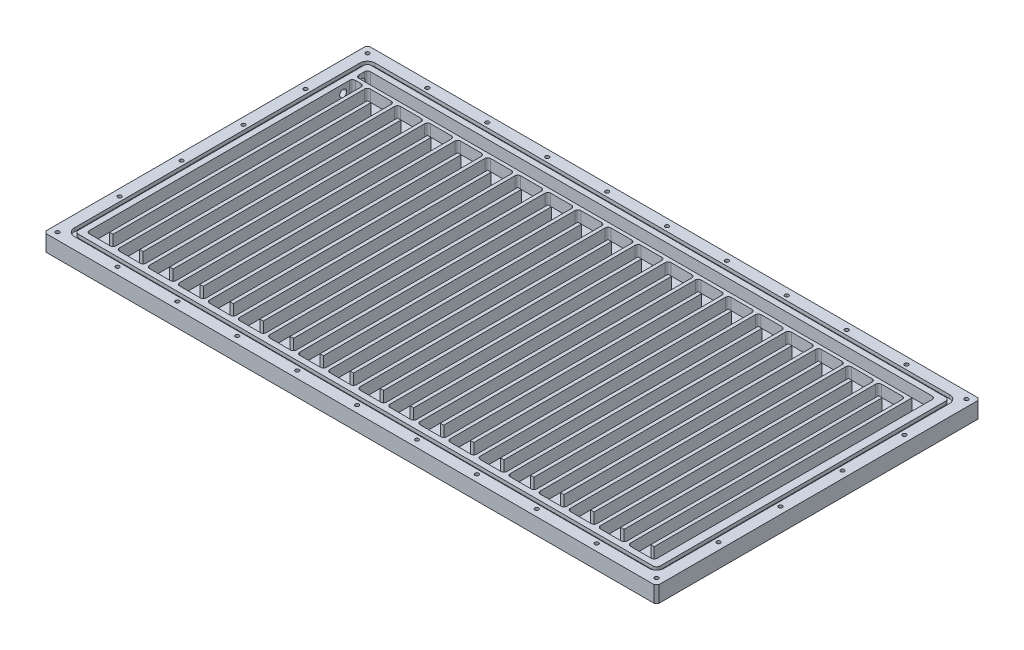
SolidWorks part; units mm, degrees
material "6063-T6"
ref_plane "Front Plane" through (0, 0, 0) normal (0, 0, 1) x (1, 0, 0)
ref_plane "Top Plane" through (0, 0, 0) normal (0, 1, 0) x (1, 0, 0)
ref_plane "Right Plane" through (0, 0, 0) normal (1, 0, 0) x (0, 0, -1)
sketch "Sketch1" plane through (0, 0, 0) normal (0, 1, 0) x (1, 0, 0)
  line L0 (265, 0) -> (265, 140)
  line L1 (0, 0) -> (265, 0)
  line L2 (0, 0) -> (0, 140)
  line L3 (0, 140) -> (265, 140)
  line L5 (213.2, 6) -> (265, 6) construction
  circle A0 centre (6, 113.2) radius 1.65 construction
  circle A1 centre (6, 59.6) radius 1.65 construction
  circle A2 centre (6, 6) radius 1.65 construction
  circle A3 centre (57.8, 6) radius 1.65 construction
  circle A4 centre (109.6, 6) radius 1.65 construction
  circle A5 centre (161.4, 6) radius 1.65 construction
  circle A6 centre (213.2, 6) radius 1.65 construction
  point P20 (265, 6)
  dimension "D3" = 3.3
  dimension "D4" = 3.3
  dimension "D5" = 3.3
  dimension "D6" = 3.3
  dimension "D7" = 3.3
  dimension "D8" = 3.3
  dimension "D9" = 3.3
  dimension "D1" = 265
  dimension "D2" = 140
  dimension "D10" = 6
  dimension "D11" = 6
  dimension "D12" = 6
  dimension "D13" = 6
  dimension "D14" = 6
  dimension "D15" = 6
  dimension "D16" = 6
  dimension "D17" = 6
  dimension "D20" = 51.8
  dimension "D21" = 51.8
  dimension "D22" = 51.8
  dimension "D23" = 51.8
  dimension "D24" = 53.6
  dimension "D25" = 53.6
  dimension "D18" = 51.8
extrude "Boss-Extrude1" add sketch "Sketch1" along normal blind 14
sketch "Sketch2" plane through (0, 14, 0) normal (0, 1, 0) x (1, 0, 0)
  line L0 (265, 140) -> (0, 140) construction
  line L1 (10, 140) -> (13.5, 140)
  line L2 (10, 140) -> (10, 10)
  line L3 (10, 10) -> (14.8949, 10)
  line L4 (13.5, 140) -> (13.5, 13.5)
  line L5 (265, 0) -> (265, 140) construction
  line L6 (14.8949, 10) -> (265, 10)
  line L8 (13.5, 13.5) -> (265, 13.5)
  line L9 (265, 10) -> (265, 13.5)
  line L10 (0, 140) -> (0, 0) construction
  line L11 (0, 0) -> (265, 0) construction
  dimension "D1" = 10
  dimension "D2" = 10
  dimension "D3" = 3.5
  dimension "D4" = 3.5
extrude "Cut-Extrude1" cut sketch "Sketch2" against normal blind 3
fillet "Fillet1" radius 3 1 edges at (13.5, 12.5, -13.5)
fillet "Fillet2" radius 6.5 1 edges at (10, 12.5, -10)
mirror "Mirror1" about plane through (265, 14, 0) normal (-1, 0, 0) of bodies 102
mirror "Mirror2" about plane through (0, 14, -140) normal (0, 0, 1) of bodies 103
hole_wizard "M4x0.7 Tapped Hole1" positions "3DSketch6" profile "Sketch13" tap size "M4x0.7" standard "BSI" end condition through all
sketch3d "3DSketch6"
  point P22 (6, 0, -113.2)
  point P24 (6, 0, -59.6)
  point P26 (6, 0, -6)
  point P28 (57.8, 0, -6)
  point P30 (109.6, 0, -6)
  point P32 (161.4, 0, -6)
  point P34 (213.2, 0, -6)
  point P36 (265, 0, -6)
cosmetic thread "Hole Thread2" parameters "D2"=4
cosmetic thread "Hole Thread3" parameters "D2"=4
cosmetic thread "Hole Thread4" parameters "D2"=4
cosmetic thread "Hole Thread5" parameters "D2"=4
cosmetic thread "Hole Thread6" parameters "D2"=4
cosmetic thread "Hole Thread7" parameters "D2"=4
cosmetic thread "Hole Thread8" parameters "D2"=4
cosmetic thread "Hole Thread9" parameters "D2"=4
sketch "Sketch13" plane through (6, 0, -113.2) normal (1, 0, 0) x (0, 0, -1)
  line L0 (0, 0) -> (0, 14)
  line L1 (0, 14) -> (1.65, 14)
  line L2 (1.65, 14) -> (1.65, 0)
  line L5 (1.65, 0) -> (0, 0)
  line L11 (0, -6.35) -> (0, 107.95) construction
  dimension "Thru Tap Drill Dia." = 3.3
  dimension "Thru Tap Drill Depth" = 14
ref_plane "Plane35" through (0, 0, -140) normal (0, 0, 1) x (1, 0, 0)
ref_plane "Plane36" through (265, 0, 0) normal (1, 0, 0) x (0, 0, -1)
mirror "Mirror3" about plane through (0, 0, -140) normal (0, 0, 1) of "M4x0.7 Tapped Hole1"
mirror "Mirror4" about plane through (265, 0, 0) normal (1, 0, 0) of "Mirror3"
sketch "Sketch3" plane through (0, 14, 0) normal (0, 1, 0) x (1, 0, 0)
  line L1 (18.5, 18.5) -> (28.5, 18.5)
  line L2 (18.5, 18.5) -> (18.5, 248.5)
  line L3 (18.5, 248.5) -> (28.5, 248.5)
  line L4 (28.5, 18.5) -> (28.5, 248.5)
  line L5 (13.5, 16.5) -> (13.5, 263.5) construction
  line L6 (513.5, 266.5) -> (16.5, 266.5) construction
  line L7 (513.5, 13.5) -> (16.5, 13.5) construction
  dimension "D1" = 10
  dimension "D2" = 5
  dimension "D3" = 18
  dimension "D4" = 5
extrude "Cut-Extrude2" cut sketch "Sketch3" against normal blind 10
pattern_linear "LPattern1" count 38 spacing 13 along (1, 0, 0) of "Cut-Extrude2"
sketch "Sketch4" plane through (0, 14, 0) normal (0, 1, 0) x (1, 0, 0)
  line L0 (31.5, 248.5) -> (31.5, 18.5) construction
  line L1 (28.5, 18.5) -> (31.5, 18.5)
  line L2 (28.5, 18.5) -> (28.5, 28.5)
  line L3 (28.5, 28.5) -> (31.5, 28.5)
  line L4 (31.5, 18.5) -> (31.5, 28.5)
  dimension "D1" = 10
extrude "Cut-Extrude3" cut sketch "Sketch4" against normal blind 10
pattern_linear "LPattern2" count 19 spacing 26 along (1, 0, 0) of "Cut-Extrude3"
sketch "Sketch5" plane through (0, 14, 0) normal (0, 1, 0) x (1, 0, 0)
  line L0 (44.5, 248.5) -> (44.5, 18.5) construction
  line L1 (41.5, 248.5) -> (44.5, 248.5)
  line L2 (41.5, 248.5) -> (41.5, 238.5)
  line L3 (41.5, 238.5) -> (44.5, 238.5)
  line L4 (44.5, 248.5) -> (44.5, 238.5)
  dimension "D1" = 10
extrude "Cut-Extrude4" cut sketch "Sketch5" against normal blind 10
pattern_linear "LPattern3" count 18 spacing 26 along (1, 0, 0) of "Cut-Extrude4"
sketch "Sketch6" plane through (0, 14, 0) normal (0, 1, 0) x (1, 0, 0)
  line L1 (18.5, 261.5) -> (509.5, 261.5)
  line L2 (18.5, 261.5) -> (18.5, 251.5)
  line L3 (18.5, 251.5) -> (499.5, 251.5)
  line L5 (18.5, 248.5) -> (18.5, 18.5) construction
  line L6 (513.5, 266.5) -> (16.5, 266.5) construction
  line L7 (499.5, 251.5) -> (499.5, 248.5)
  line L12 (499.5, 248.5) -> (509.5, 248.5)
  line L13 (509.5, 248.5) -> (509.5, 261.5)
  dimension "D1" = 90
  dimension "D2" = 270
  dimension "D3" = 0
  dimension "D4" = 5
  dimension "D5" = 10
extrude "Cut-Extrude5" cut sketch "Sketch6" against normal blind 10
fillet "Fillet3" radius 2.5 76 edges at (18.5, 9, -18.5) (41.5, 9, -18.5) (44.5, 9, -18.5) (67.5, 9, -18.5) (70.5, 9, -18.5) (93.5, 9, -18.5) (96.5, 9, -18.5) (119.5, 9, -18.5) (122.5, 9, -18.5) (145.5, 9, -18.5) (148.5, 9, -18.5) (171.5, 9, -18.5) (174.5, 9, -18.5) (197.5, 9, -18.5) (200.5, 9, -18.5) (223.5, 9, -18.5) (226.5, 9, -18.5) (249.5, 9, -18.5) (252.5, 9, -18.5) (275.5, 9, -18.5) (278.5, 9, -18.5) (301.5, 9, -18.5) (304.5, 9, -18.5) (327.5, 9, -18.5) (330.5, 9, -18.5) (353.5, 9, -18.5) (356.5, 9, -18.5) (379.5, 9, -18.5) (382.5, 9, -18.5) (405.5, 9, -18.5) (408.5, 9, -18.5) (431.5, 9, -18.5) (434.5, 9, -18.5) (457.5, 9, -18.5) (460.5, 9, -18.5) (483.5, 9, -18.5) (486.5, 9, -18.5) (509.5, 9, -18.5) (473.5, 9, -248.5) (447.5, 9, -248.5) (421.5, 9, -248.5) (395.5, 9, -248.5) (369.5, 9, -248.5) (343.5, 9, -248.5) (317.5, 9, -248.5) (291.5, 9, -248.5) (265.5, 9, -248.5) (239.5, 9, -248.5) (213.5, 9, -248.5) (187.5, 9, -248.5) (161.5, 9, -248.5) (135.5, 9, -248.5) (109.5, 9, -248.5) (57.5, 9, -248.5) (31.5, 9, -248.5) (496.5, 9, -248.5) (470.5, 9, -248.5) (444.5, 9, -248.5) (418.5, 9, -248.5) (392.5, 9, -248.5) (366.5, 9, -248.5) (340.5, 9, -248.5) (314.5, 9, -248.5) (288.5, 9, -248.5) (262.5, 9, -248.5) (236.5, 9, -248.5) (210.5, 9, -248.5) (83.5, 9, -248.5) (106.5, 9, -248.5) (184.5, 9, -248.5) (158.5, 9, -248.5) (132.5, 9, -248.5) (80.5, 9, -248.5) (54.5, 9, -248.5) (28.5, 9, -248.5) (509.5, 9, -261.5)
sketch "Sketch7" plane through (0, 0, 0) normal (-1, 0, 0) x (0, 0, 1)
  line L2 (-280, 14) -> (-280, 0) construction
  line L4 (-280, 14) -> (0, 14) construction
  circle A0 centre (-256.5, 7) radius 4.35
  dimension "D1" = 8.7
  dimension "D2" = 7
  dimension "D3" = 23.5
fillet "Fillet4" radius 2.5 1 edges at (18.5, 9, -248.5)
ref_plane "Plane33" through (265, 0, 0) normal (-1, 0, 0) x (0, 0, 1)
ref_plane "Plane34" through (0, 0, -140) normal (0, 0, 1) x (1, 0, 0)
chamfer "Chamfer1" distance 2 angle 45 4 edges at (530, 7, -280) (530, 7, 0) (0, 7, 0) (0, 7, -280)
hole_wizard "G1/8 Tapped Hole1" positions "3DSketch1" profile "Sketch8" tap size "G1/8" standard "BSI"
sketch3d "3DSketch1"
  point P0 (0, 7, -256.5)
sketch "Sketch8" plane through (0, 7, -256.5) normal (0, 1, 0) x (0, 0, 1)
  line L0 (0, 0) -> (0, 11.3638)
  line L1 (0, 11.3638) -> (4.4, 8.72)
  line L2 (4.4, 8.72) -> (4.4, 0)
  line L5 (4.4, 0) -> (0, 0)
  line L10 (0, 11.3638) -> (-4.4, 8.72) construction
  line L11 (0, -6.35) -> (0, 107.95) construction
  dimension "Tap Drill Dia." = 8.8
  dimension "Tap Drill Depth" = 8.72
  dimension "Drill Angle" = 118
cosmetic thread "Hole Thread1" parameters "D1"=6, "D2"=9.728
fillet "Fillet5" radius 2.5 2 edges at (18.5, 9, -251.5) (18.5, 9, -261.5)
hole_wizard "Ø6.0 (6) Diameter Hole1" positions "3DSketch2" profile "Sketch10" hole size "Ø6.0" standard "BSI"
sketch3d "3DSketch2"
  point P0 (0, 7, -256.5)
sketch "Sketch10" plane through (0, 7, -256.5) normal (0, 1, 0) x (0, 0, 1)
  line L0 (0, 0) -> (0, 23.8026)
  line L1 (0, 23.8026) -> (3, 22)
  line L2 (3, 22) -> (3, 0)
  line L5 (3, 0) -> (0, 0)
  line L10 (0, 23.8026) -> (-3, 22) construction
  line L11 (0, -6.35) -> (0, 107.95) construction
  dimension "Hole Dia." = 6
  dimension "Hole Depth" = 22
  dimension "Drill Angle" = 118
pattern_linear "LPattern10" count 2 spacing 16 along (0, 0, 1) of "G1/8 Tapped Hole1", "Ø6.0 (6) Diameter Hole1"
equation "\"D1@Sketch1\"=530/2"
equation "\"D2@Sketch1\"=280/2"
equation "\"D4@Sketch1\"=\"D3@Sketch1\""
equation "\"D5@Sketch1\"=\"D3@Sketch1\""
equation "\"D6@Sketch1\"=\"D3@Sketch1\""
equation "\"D7@Sketch1\"=\"D3@Sketch1\""
equation "\"D8@Sketch1\"=\"D3@Sketch1\""
equation "\"D9@Sketch1\"=\"D3@Sketch1\""
equation "\"D11@Sketch1\"=\"D10@Sketch1\""
equation "\"D12@Sketch1\"=\"D10@Sketch1\""
equation "\"D14@Sketch1\"=\"D13@Sketch1\""
equation "\"D15@Sketch1\"=\"D13@Sketch1\""
equation "\"D16@Sketch1\"=\"D13@Sketch1\""
equation "\"D17@Sketch1\"=\"D13@Sketch1\""
equation "\"D23@Sketch1\"=\"D22@Sketch1\""
equation "\"D22@Sketch1\"=\"D20@Sketch1\""
equation "\"D21@Sketch1\"=\"D20@Sketch1\""
equation "\"D25@Sketch1\"=\"D24@Sketch1\""
equation "\"D20@Sketch1\"=(530-2*\"D10@Sketch1\")/10"
equation "\"D24@Sketch1\"=(280-2*\"D13@Sketch1\")/5"
equation "\"D18@Sketch1\"=\"D23@Sketch1\""
